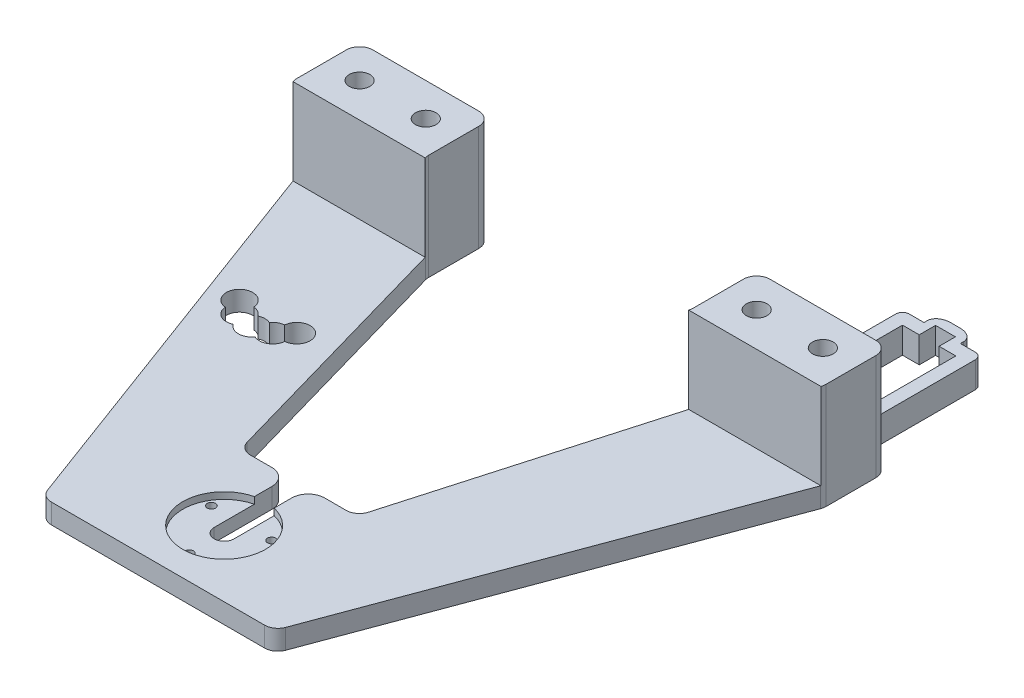
SolidWorks part; units mm, degrees
ref_plane "Front Plane" through (0, 0, 0) normal (0, 0, 1) x (1, 0, 0)
ref_plane "Top Plane" through (0, 0, 0) normal (0, 1, 0) x (1, 0, 0)
ref_plane "Right Plane" through (0, 0, 0) normal (1, 0, 0) x (0, 0, -1)
sketch "Sketch1" plane through (0, 0, 0) normal (0, 1, 0) x (1, 0, 0)
  line L0 (-96.52, 178.9428) -> (-55.88, 178.9428)
  line L1 (-50.8, 173.8628) -> (-50.8, 154.6109)
  line L3 (-101.6, 154.8128) -> (-101.6, 173.8628)
  line L4 (0, 53.8) -> (-18.3922, 53.8)
  line L6 (-40.9175, 0) -> (0, 0)
  line L8 (-101.2823, 153.0443) -> (-45.6797, 3.3116)
  line L9 (0, 53.8) -> (0, 0)
  line L10 (-23.2771, 57.4855) -> (-50.6049, 153.2164)
  circle A0 centre (-88.9, 166.2428) radius 3.9687
  circle A1 centre (-63.5, 166.2428) radius 3.9688
  arc A2 (-55.88, 178.9428) -> (-50.8, 173.8628) centre (-55.88, 173.8628) cw
  arc A3 (-96.52, 178.9428) -> (-101.6, 173.8628) centre (-96.52, 173.8628) ccw
  arc A4 (-101.2823, 153.0443) -> (-101.6, 154.8128) centre (-96.52, 154.8128) cw
  arc A5 (-45.6797, 3.3116) -> (-40.9175, 0) centre (-40.9175, 5.08) ccw
  arc A6 (-18.3922, 53.8) -> (-23.2771, 57.4855) centre (-18.3922, 58.88) cw
  arc A7 (-50.8, 154.6109) -> (-50.6049, 153.2164) centre (-45.72, 154.6109) ccw
  point P18 (-50.8, 178.9428)
  point P21 (-101.6, 178.9428)
  point P47 (0, 26.9)
  point P51 (-101.6, 153.9)
  point P54 (-44.45, 0)
  point P57 (-22.225, 53.8)
  point P60 (-50.8, 153.9)
  dimension "D3" = 7.9375
  dimension "D6" = 5.08
  dimension "D13" = 5.08
  dimension "D14" = 5.08
  dimension "D15" = 5.08
  dimension "D16" = 5.08
  dimension "D1" = 50.8
  dimension "D2" = 19.05
  dimension "D4" = 12.7
  dimension "D5" = 12.7
  dimension "D7" = 101.6
  dimension "D8" = 127
  dimension "D9" = 12.7
  dimension "D10" = 44.45
  dimension "D11" = 22.225
  dimension "D12" = 53.8
extrude "Boss-Extrude2" add sketch "Sketch1" along normal blind 40.64
mirror "Mirror1" about plane through (0, 40.64, -53.8) normal (-1, 0, 0) of "Boss-Extrude2"
sketch "Sketch4" plane through (0, 40.64, 0) normal (0, 1, 0) x (1, 0, 0)
  line L2 (18.3922, 53.8) -> (-18.3922, 53.8) construction
  circle A0 centre (11.5484, 32.0195) radius 1.5875
  circle A1 centre (0, 12.017) radius 1.5875
  circle A2 centre (-11.5484, 32.0195) radius 1.5875
  point P9 (0, 25.352)
  dimension "D1" = 3.175
  dimension "D3" = 28.448
  dimension "D4" = 13.335
  dimension "D2" = 3
extrude "Cut-Extrude1" cut sketch "Sketch4" against normal through all
sketch "Sketch5" plane through (0, 0, 0) normal (0, 1, 0) x (1, 0, 0)
  line L0 (18.3922, 53.8) -> (-18.3922, 53.8) construction
  circle A0 centre (0, 25.352) radius 15.875
  dimension "D2" = 31.75
  dimension "D1" = 28.448
extrude "Cut-Extrude2" cut sketch "Sketch5" along normal blind 5.08 from offset 5.08
sketch "Sketch7" plane through (0, 40.64, 0) normal (0, 1, 0) x (1, 0, 0)
  line L1 (-155.1296, 153.0819) -> (166.308, 153.0819)
  line L2 (-155.1296, 153.0819) -> (-155.1296, 0)
  line L3 (-155.1296, 0) -> (166.308, 0)
  line L4 (166.308, 153.0819) -> (166.308, 0)
  line L5 (-40.9175, 0) -> (40.9175, 0) construction
extrude "Cut-Extrude3" cut sketch "Sketch7" against normal offset from surface (33.02 mm away) 33.02 up to face at (11.5484, 40.64, -30.432)
sketch "Sketch8" plane through (0, 0, 0) normal (0, 1, 0) x (1, 0, 0)
  line L0 (0, 25.352) -> (0, 53.8) construction
  line L1 (18.3922, 53.8) -> (-18.3922, 53.8) construction
  line L2 (-3.81, 25.352) -> (-3.81, 53.8)
  line L3 (3.81, 25.352) -> (3.81, 53.8)
  arc A0 (-3.81, 25.352) -> (3.81, 25.352) centre (0, 25.352) ccw
  arc A1 (3.81, 53.8) -> (-3.81, 53.8) centre (0, 53.8) ccw
  point P5 (0, 39.576)
  dimension "D1" = 7.62
extrude "Cut-Extrude5" cut sketch "Sketch8" along direction (0, 1, 0) on the side of the normal through all
fillet "Fillet1" radius 6.35 1 edges at (-3.81, 3.81, -53.8) type face fillet first side face at (-11.1011, 3.81, -53.8) second side face at (-3.81, 4.2333, -39.9717)
fillet "Fillet2" radius 6.35 1 edges at (3.81, 3.81, -53.8) type face fillet first side face at (11.1011, 3.81, -53.8) second side face at (3.81, 4.2333, -39.9717)
sketch "Sketch9" plane through (0, 0, 0) normal (0, 1, 0) x (1, 0, 0)
  line L0 (-63.5, 166.2428) -> (-63.5, 178.9428) construction
  line L2 (-88.9, 166.2428) -> (-88.9, 178.9428) construction
  line L3 (-88.9, 166.2428) -> (-63.5, 166.2428) construction
  line L4 (-91.44, 173.9428) -> (-91.44, 224.7428)
  line L5 (-91.44, 224.7428) -> (-60.96, 224.7428)
  line L6 (-60.96, 224.7428) -> (-60.96, 173.9428)
  line L7 (-60.96, 173.9428) -> (-91.44, 173.9428)
  line L8 (-55.88, 178.9428) -> (-96.52, 178.9428) construction
  point P13 (-76.2, 173.9428)
  point P14 (-76.2, 166.2428)
  dimension "D1" = 30.48
  dimension "D2" = 50.8
  dimension "D3" = 5
extrude "Extrude-Thin1" add sketch "Sketch9" along normal blind 10 thin thin type one direction reverse wall 5
sketch "Sketch14" plane through (0, 0, 0) normal (0, -1, 0) x (1, 0, 0)
  line L0 (-65.96, -178.9428) -> (-86.44, -178.9428) construction
  line L1 (-81.2, -174.9428) -> (-71.2, -174.9428) construction
  line L2 (-76.2, -178.9428) -> (-76.2, -173.6531) construction
  circle A0 centre (-81.2, -174.9428) radius 1.95
  circle A1 centre (-71.2, -174.9428) radius 1.95
  point P6 (-76.2, -174.9428)
  dimension "D1" = 3.9
  dimension "D4" = 3.9
  dimension "D2" = 4
  dimension "D3" = 10
extrude "Cut-Extrude6" cut sketch "Sketch14" against normal blind 20
ref_plane "Plane2" through (-60.96, 10, -178.9428) normal (-1, 0, 0) x (0, 0, 1)
ref_plane "Plane3" through (-76.2, 0, 0) normal (1, 0, 0) x (0, 0, -1)
sketch "Sketch18" plane through (-60.96, 10, -178.9428) normal (-1, 0, 0) x (0, 0, 1)
  line L0 (-1.27, 0) -> (0, 1.524)
  line L1 (-45.8, 0) -> (0, 0) construction
  line L2 (0, 30.64) -> (0, -10) construction
  line L3 (0, 1.524) -> (0, 0)
  line L4 (0, 0) -> (-1.27, 0)
  dimension "D1" = 1.524
  dimension "D2" = 1.27
extrude "Boss-Extrude4" add sketch "Sketch18" along normal up to vertex (5 mm away) up to point (-65.96, 10, -178.9428)
mirror "Mirror3" about plane through (-76.2, 0, 0) normal (1, 0, 0) of "Boss-Extrude4"
mirror "Mirror5" about plane through (0, 0, 0) normal (1, 0, 0) of "Mirror3", "Boss-Extrude4", "Cut-Extrude6", "Extrude-Thin1"
fillet "Fillet3" radius 2.54 4 edges at (-91.44, 5, -224.7428) (-60.96, 5, -224.7428) (60.96, 5, -224.7428) (91.44, 5, -224.7428)
sketch "Sketch19" plane through (0, 0, -224.7428) normal (0, 0, -1) x (-1, 0, 0)
  line L1 (72.39, 10) -> (80.01, 10)
  line L2 (72.39, 10) -> (72.39, -0.16)
  line L3 (72.39, -0.16) -> (80.01, -0.16)
  line L4 (80.01, 10) -> (80.01, -0.16)
  line L9 (63.5, 10) -> (88.9, 10) construction
  line L10 (76.2, 38.5994) -> (76.2, -38.5994) construction
  point P6 (76.2, 10)
  dimension "D1" = 7.62
  dimension "D2" = 10.16
sketch "Sketch20" plane through (0, 0, 0) normal (0, 1, 0) x (1, 0, 0)
  line L0 (-63.5, 224.7428) -> (-88.9, 224.7428) construction
  line L1 (-83.185, 224.7428) -> (-69.215, 224.7428)
  line L2 (-83.185, 224.7428) -> (-83.185, 229.8228)
  line L3 (-83.185, 229.8228) -> (-69.215, 229.8228)
  line L4 (-69.215, 224.7428) -> (-69.215, 229.8228)
  line L5 (-76.2, -38.5994) -> (-76.2, 38.5994) construction
  dimension "D1" = 13.97
  dimension "D2" = 5.08
  dimension "D3" = 6.985
extrude "Boss-Extrude5" add sketch "Sketch20" along normal up to vertex (10 mm away) up to point (-88.9, 10, -224.7428)
fillet "Fillet7" radius 3.81 1 edges at (-83.185, 5, -229.8228) second distance 5.08 first distance on face at (-83.185, 5, -227.2828)
fillet "Fillet6" radius 3.81 1 edges at (-69.215, 5, -229.8228) second distance 5.08 first distance on face at (-69.215, 5, -227.2828)
extrude "Cut-Extrude10" cut sketch "Sketch19" against normal up to surface (5 mm away) and the other way blind 1.27 up to face at (-76.2, 5, -219.7428)
mirror "Mirror6" about plane through (0, 0, 0) normal (1, 0, 0) of "Cut-Extrude6", "Cut-Extrude10", "Fillet6", "Fillet7", "Boss-Extrude5"
sketch "Sketch21" plane through (0, 0, -178.9428) normal (0, 0, -1) x (-1, 0, 0)
  line L1 (40.2088, 57.3257) -> (117.296, 57.3257)
  line L2 (40.2088, 57.3257) -> (40.2088, -11.7482)
  line L3 (40.2088, -11.7482) -> (117.296, -11.7482)
  line L4 (117.296, 57.3257) -> (117.296, -11.7482)
extrude "Cut-Extrude11" cut sketch "Sketch21" along normal through all
sketch "Sketch22" plane through (0, 0, 0) normal (0, -1, 0) x (1, 0, 0)
  line L0 (-60.96, -123.9428) -> (-60.96, -233.9428) construction
  circle A0 centre (-60.96, -109.5725) radius 4.953
  point P2 (-56.6011, -109.6401)
  point P3 (-60.96, -109.5725)
  dimension "D1" = 9.906
extrude "Boss-Extrude6" add sketch "Sketch22" along normal blind 10.16
sketch "Sketch23" plane through (0, 0, 0) normal (0, -1, 0) x (1, 0, 0)
  line L0 (-60.96, -123.9428) -> (-60.96, -233.9428) construction
  line L1 (-60.96, -109.5725) -> (-60.96, -96.8725) construction
  line L2 (-60.96, -109.5725) -> (-60.96, -96.8725) construction
  circle A1 centre (-67.31, -98.5739) radius 5.08
  circle A13 centre (-60.96, -96.8725) radius 5.08
  circle A14 centre (-60.96, -109.5725) radius 4.953 construction
  circle A15 centre (-71.9585, -103.2225) radius 5.08
  circle A16 centre (-54.61, -98.5739) radius 5.08
  circle A17 centre (-49.9615, -103.2225) radius 5.08
  point P5 (-60.96, -109.5725)
  dimension "D1" = 10.16
  dimension "D2" = 12.7
  dimension "D3" = 3
  dimension "D4" = 12.7
  dimension "D6" = 12.7
  dimension "D5" = 3
extrude "Cut-Extrude12" cut sketch "Sketch23" against normal through all contours A1 A15 | A1 A15 | A15 A1 A13 | A1 A13 | A16 A13 A1 | A13 A16 | A17 A16 A13 | A16 A17 | A16 A17 region at (-64.135, 0, -97.7232) region at (-60.96, 0, -96.1) region at (-67.6962, 0, -97.905) region at (-69.6343, 0, -100.8982) region at (-72.6842, 0, -103.9481) region at (-54.2238, 0, -97.905) region at (-57.785, 0, -97.7232) region at (-49.2358, 0, -103.9481) region at (-52.2857, 0, -100.8982)
